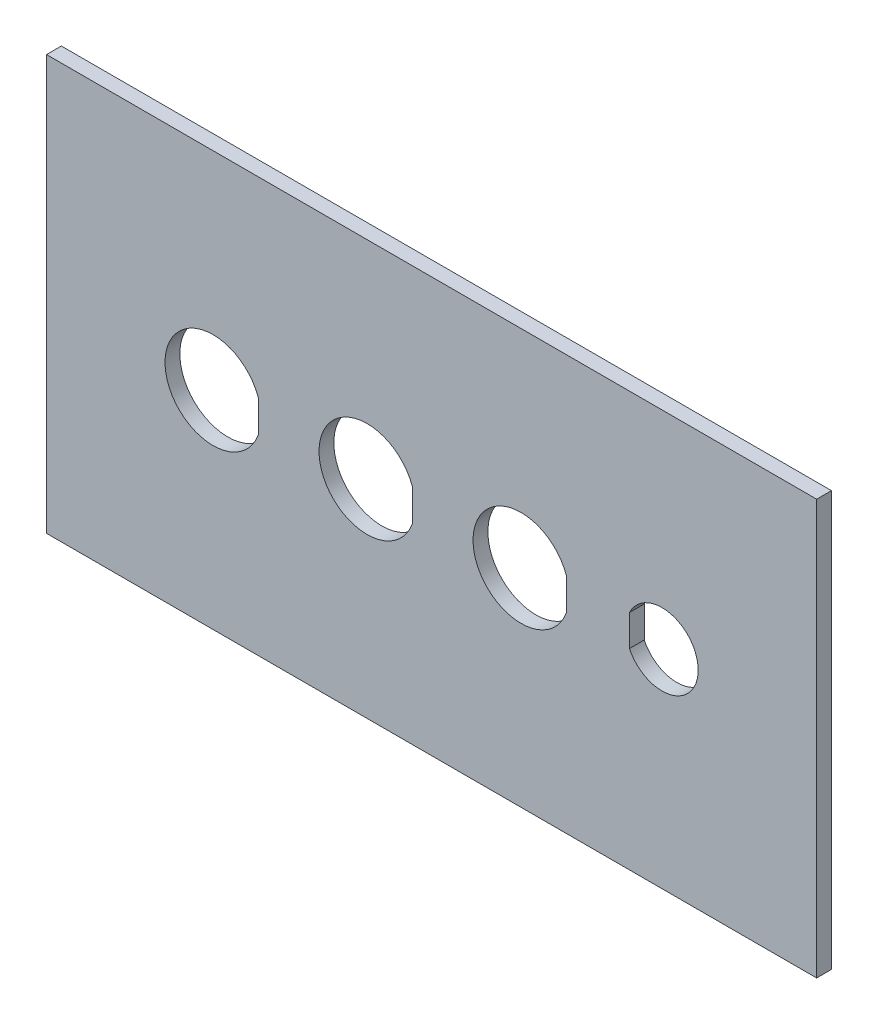
SolidWorks part; units mm, degrees
ref_plane "Front Plane" through (0, 0, 0) normal (0, 0, 1) x (1, 0, 0)
ref_plane "Top Plane" through (0, 0, 0) normal (0, 1, 0) x (1, 0, 0)
ref_plane "Right Plane" through (0, 0, 0) normal (1, 0, 0) x (0, 0, -1)
sketch "Sketch1" plane through (0, 0, 0) normal (0, 0, 1) x (1, 0, 0)
  line L1 (-73.1988, 43.9567) -> (91.9012, 43.9567)
  line L2 (-73.1988, 43.9567) -> (-73.1988, -44.9433)
  line L3 (-73.1988, -44.9433) -> (91.9012, -44.9433)
  line L4 (91.9012, 43.9567) -> (91.9012, -44.9433)
  line L5 (-73.1988, 43.9567) -> (91.9012, -44.9433) construction
  line L6 (-73.1988, -44.9433) -> (91.9012, 43.9567) construction
  line L8 (-73.1988, -0.4933) -> (91.9012, -0.4933) construction
  line L12 (51.7692, 2.8571) -> (51.7692, -3.8438)
  line L13 (-27.7988, 2.9708) -> (-27.7988, -3.9574)
  line L14 (5.2212, 2.9708) -> (5.2212, -3.9574)
  line L15 (38.2412, 2.9708) -> (38.2412, -3.9574)
  line L17 (-60.4988, 24.9067) -> (79.2012, 24.9067) construction
  line L18 (-60.4988, 24.9067) -> (-60.4988, -25.8933) construction
  line L19 (-60.4988, -25.8933) -> (79.2012, -25.8933) construction
  line L20 (79.2012, 24.9067) -> (79.2012, -25.8933) construction
  line L21 (-60.4988, 24.9067) -> (79.2012, -25.8933) construction
  line L22 (-60.4988, -25.8933) -> (79.2012, 24.9067) construction
  arc A6 (51.7692, -3.8438) -> (51.7692, 2.8571) centre (58.7542, -0.4933) ccw
  arc A7 (-27.7988, 2.9708) -> (-27.7988, -3.9574) centre (-37.4988, -0.4933) ccw
  arc A8 (5.2212, 2.9708) -> (5.2212, -3.9574) centre (-4.4788, -0.4933) ccw
  arc A9 (38.2412, 2.9708) -> (38.2412, -3.9574) centre (28.5412, -0.4933) ccw
  point P0 (9.3512, -0.4933)
  point P5 (66.5012, -0.4933)
  point P11 (-47.7988, -0.4933)
  dimension "D3" = 14.732
  dimension "D6" = 25.4
  dimension "D4" = 15.494
  dimension "D5" = 20.6
  dimension "D1" = 165.1
  dimension "3.5" = 88.9
  dimension "D7" = 25.4
  dimension "D8" = 20
  dimension "D9" = 3
  dimension "D10" = 139.7
  dimension "D11" = 50.8
extrude "Boss-Extrude1" add sketch "Sketch1" along normal blind 3.175
